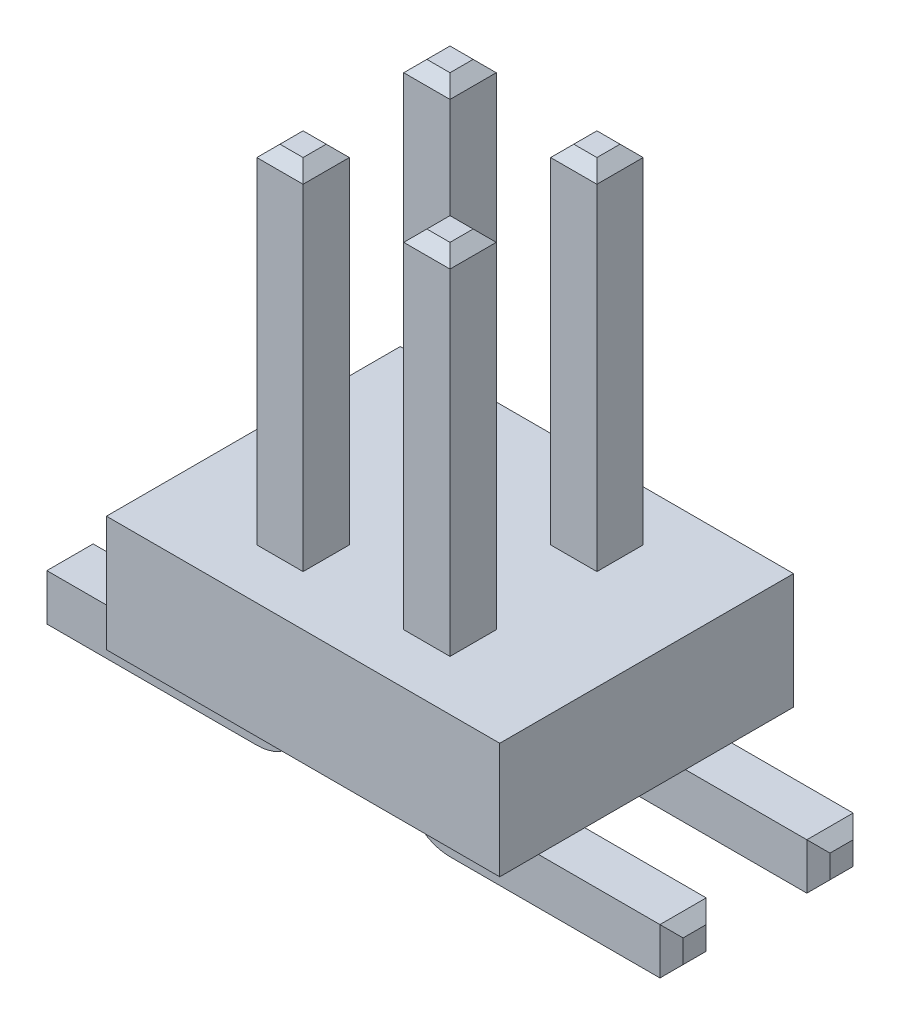
SolidWorks part; units mm, degrees
ref_plane "Vorne" through (0, 0, 0) normal (0, 0, 1) x (1, 0, 0)
ref_plane "Oben" through (0, 0, 0) normal (0, 1, 0) x (1, 0, 0)
ref_plane "Rechts" through (0, 0, 0) normal (1, 0, 0) x (0, 0, -1)
sketch "Skizze1" plane through (0, 0, 0) normal (0, 0, 1) x (1, 0, 0)
  line L1 (0, 0) -> (3.4, 0)
  line L2 (0, 0) -> (0, 1)
  line L3 (0, 1) -> (3.4, 1)
  line L4 (3.4, 0) -> (3.4, 1)
  dimension "D1" = 3.4
  dimension "D2" = 1
extrude "Aufsatz-Linear austragen1" add sketch "Skizze1" along normal blind 2.54
sketch "Skizze3" plane through (0, 0, 0) normal (0, -1, 0) x (1, 0, 0)
  line L16 (0.865, 1.705) -> (1.265, 1.705)
  line L17 (0.865, 1.705) -> (0.865, 2.105)
  line L18 (0.865, 2.105) -> (1.265, 2.105)
  line L19 (1.265, 1.705) -> (1.265, 2.105)
  line L20 (0.865, 1.705) -> (1.265, 2.105) construction
  line L21 (0.865, 2.105) -> (1.265, 1.705) construction
  line L22 (2.135, 1.705) -> (2.535, 1.705)
  line L23 (2.135, 1.705) -> (2.135, 2.105)
  line L24 (2.135, 2.105) -> (2.535, 2.105)
  line L25 (2.535, 1.705) -> (2.535, 2.105)
  line L26 (2.135, 1.705) -> (2.535, 2.105) construction
  line L27 (2.135, 2.105) -> (2.535, 1.705) construction
  line L28 (0.865, 0.435) -> (1.265, 0.435)
  line L29 (0.865, 0.435) -> (0.865, 0.835)
  line L30 (0.865, 0.835) -> (1.265, 0.835)
  line L31 (1.265, 0.435) -> (1.265, 0.835)
  line L32 (0.865, 0.435) -> (1.265, 0.835) construction
  line L33 (0.865, 0.835) -> (1.265, 0.435) construction
  line L34 (2.135, 0.435) -> (2.535, 0.435)
  line L35 (2.135, 0.435) -> (2.135, 0.835)
  line L36 (2.135, 0.835) -> (2.535, 0.835)
  line L37 (2.535, 0.435) -> (2.535, 0.835)
  line L38 (2.135, 0.435) -> (2.535, 0.835) construction
  line L39 (2.135, 0.835) -> (2.535, 0.435) construction
  line L40 (0.865, 2.975) -> (1.265, 2.975)
  line L41 (0.865, 2.975) -> (0.865, 3.375)
  line L42 (0.865, 3.375) -> (1.265, 3.375)
  line L43 (1.265, 2.975) -> (1.265, 3.375)
  line L44 (2.135, 2.975) -> (2.535, 2.975)
  line L45 (2.135, 2.975) -> (2.135, 3.375)
  line L46 (2.135, 3.375) -> (2.535, 3.375)
  line L47 (2.535, 2.975) -> (2.535, 3.375)
  line L48 (0.865, 2.975) -> (1.265, 3.375) construction
  line L49 (0.865, 3.375) -> (1.265, 2.975) construction
  line L50 (2.135, 2.975) -> (2.535, 3.375) construction
  line L51 (2.135, 3.375) -> (2.535, 2.975) construction
  point P1 (2.335, 3.175)
  point P2 (1.065, 3.175)
  point P17 (1.065, 1.905)
  point P22 (2.335, 1.905)
  point P27 (1.065, 0.635)
  point P32 (2.335, 0.635)
extrude "Aufsatz-Linear austragen3" add sketch "Skizze3" along normal blind 0.5
sketch "Skizze4" plane through (2.535, 0, 0) normal (1, 0, 0) x (0, 0, -1)
  line L5 (-1.705, -0.5) -> (-1.705, 0) construction
  line L6 (-2.105, -0.5) -> (-1.705, -0.5)
  line L7 (-2.105, -0.5) -> (-2.105, -0.1)
  line L8 (-2.105, -0.1) -> (-1.705, -0.1)
  line L9 (-1.705, -0.5) -> (-1.705, -0.1)
  line L10 (-0.435, -0.5) -> (-0.435, 0) construction
  line L11 (-0.835, -0.5) -> (-0.435, -0.5)
  line L12 (-0.835, -0.5) -> (-0.835, -0.1)
  line L13 (-0.835, -0.1) -> (-0.435, -0.1)
  line L14 (-0.435, -0.5) -> (-0.435, -0.1)
  dimension "D1" = 0.4
  dimension "D2" = 0.4
extrude "Aufsatz-Linear austragen4" add sketch "Skizze4" along normal blind 1.915
sketch "Skizze5" plane through (0.865, 0, 0) normal (-1, 0, 0) x (0, 0, 1)
  line L0 (1.705, -0.5) -> (1.705, 0) construction
  line L5 (2.105, -0.5) -> (1.705, -0.5)
  line L6 (2.105, -0.5) -> (2.105, -0.1)
  line L7 (2.105, -0.1) -> (1.705, -0.1)
  line L8 (1.705, -0.5) -> (1.705, -0.1)
  line L9 (0.435, -0.5) -> (0.435, 0) construction
  line L10 (0.835, -0.5) -> (0.435, -0.5)
  line L11 (0.835, -0.5) -> (0.835, -0.1)
  line L12 (0.835, -0.1) -> (0.435, -0.1)
  line L13 (0.435, -0.5) -> (0.435, -0.1)
extrude "Aufsatz-Linear austragen5" add sketch "Skizze5" along normal blind 1.915
sketch "Skizze6" plane through (0, 1, 0) normal (0, 1, 0) x (1, 0, 0)
  line L0 (3.4, 0) -> (0, 0) construction
  line L1 (0.865, -0.835) -> (1.265, -0.835)
  line L2 (0.865, -0.835) -> (0.865, -0.435)
  line L3 (0.865, -0.435) -> (1.265, -0.435)
  line L4 (1.265, -0.835) -> (1.265, -0.435)
  line L5 (0.865, -0.835) -> (1.265, -0.435) construction
  line L6 (0.865, -0.435) -> (1.265, -0.835) construction
  line L7 (0, -2.54) -> (0, 0) construction
  line L8 (2.135, -0.835) -> (2.535, -0.835)
  line L9 (2.135, -0.835) -> (2.135, -0.435)
  line L10 (2.135, -0.435) -> (2.535, -0.435)
  line L11 (2.535, -0.835) -> (2.535, -0.435)
  line L12 (2.135, -0.835) -> (2.535, -0.435) construction
  line L13 (2.135, -0.435) -> (2.535, -0.835) construction
  line L14 (0.865, -2.105) -> (1.265, -2.105)
  line L15 (0.865, -2.105) -> (0.865, -1.705)
  line L16 (0.865, -1.705) -> (1.265, -1.705)
  line L17 (1.265, -2.105) -> (1.265, -1.705)
  line L18 (0.865, -2.105) -> (1.265, -1.705) construction
  line L19 (0.865, -1.705) -> (1.265, -2.105) construction
  line L20 (2.135, -2.105) -> (2.535, -2.105)
  line L21 (2.135, -2.105) -> (2.135, -1.705)
  line L22 (2.135, -1.705) -> (2.535, -1.705)
  line L23 (2.535, -2.105) -> (2.535, -1.705)
  line L24 (2.135, -2.105) -> (2.535, -1.705) construction
  line L25 (2.135, -1.705) -> (2.535, -2.105) construction
  point P0 (1.065, -0.635)
  point P11 (2.335, -0.635)
  point P16 (1.065, -1.905)
  point P21 (2.335, -1.905)
  dimension "D1" = 0.4
  dimension "D2" = 0.4
  dimension "D3" = 0.635
  dimension "D4" = 1.065
  dimension "D5" = 2
extrude "Aufsatz-Linear austragen6" add sketch "Skizze6" along normal blind 3
chamfer "Fase2" distance 0.1 angle 45 32 edges at (-1.05, -0.1, 1.905) (-1.05, -0.3, 2.105) (-1.05, -0.5, 1.905) (-1.05, -0.3, 1.705) (-1.05, -0.1, 0.635) (-1.05, -0.3, 0.835) (-1.05, -0.5, 0.635) (-1.05, -0.3, 0.435) (4.45, -0.3, 0.835) (4.45, -0.1, 0.635) (4.45, -0.3, 0.435) (4.45, -0.5, 0.635) (4.45, -0.3, 1.705) (4.45, -0.5, 1.905) (4.45, -0.3, 2.105) (4.45, -0.1, 1.905) (2.535, 4, 1.905) (2.335, 4, 2.105) (2.135, 4, 1.905) (2.335, 4, 1.705) (2.335, 4, 0.835) (2.535, 4, 0.635) (2.335, 4, 0.435) (2.135, 4, 0.635) (1.065, 4, 0.835) (1.265, 4, 0.635) (1.065, 4, 0.435) (0.865, 4, 0.635) (1.065, 4, 1.705) (0.865, 4, 1.905) (1.065, 4, 2.105) (1.265, 4, 1.905)
fillet "Verrundung1" radius 0.1 4 edges at (0.865, -0.1, 1.905) (0.865, -0.1, 0.635) (2.535, -0.1, 1.905) (2.535, -0.1, 0.635)
fillet "Verrundung2" radius 0.4 4 edges at (1.265, -0.5, 1.905) (2.135, -0.5, 1.905) (2.135, -0.5, 0.635) (1.265, -0.5, 0.635)
